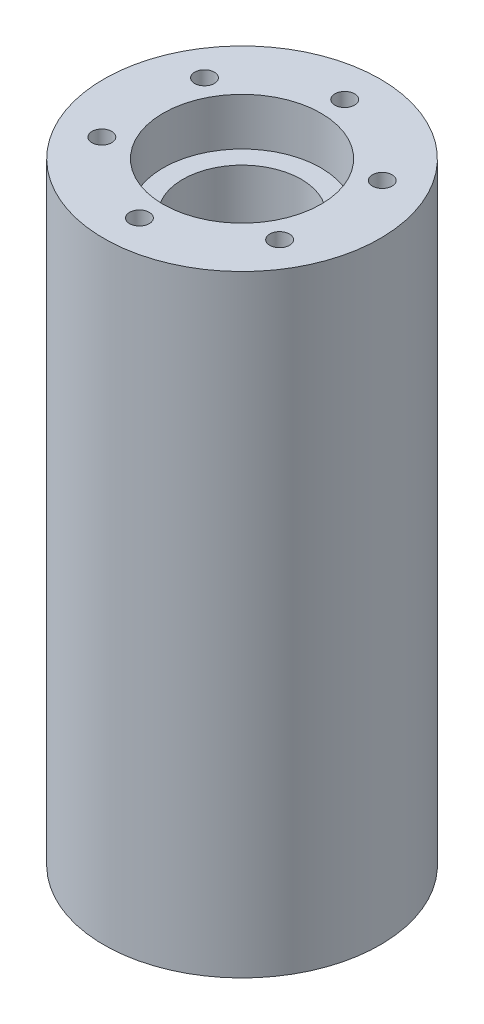
SolidWorks part; units mm, degrees
material "PA38 (3.3206)"
ref_plane "Płaszczyzna przednia" through (0, 0, 0) normal (0, 0, 1) x (1, 0, 0)
ref_plane "Płaszczyzna górna" through (0, 0, 0) normal (0, 1, 0) x (1, 0, 0)
ref_plane "Płaszczyzna prawa" through (0, 0, 0) normal (1, 0, 0) x (0, 0, -1)
sketch "Szkic1" plane through (0, 0, 0) normal (1, 0, 0) x (0, 0, -1)
  line L0 (0, -77.5) -> (0, 77.5) construction
  line L1 (-23.5, -77.5) -> (-35, -77.5)
  line L2 (-35, -77.5) -> (-35, 77.5)
  line L3 (-35, 77.5) -> (-20, 77.5)
  line L4 (-20, 77.5) -> (-20, 65.5)
  line L5 (-20, 65.5) -> (-15, 65.5)
  line L6 (-15, 65.5) -> (-15, -63.5)
  line L7 (-15, -63.5) -> (-23.5, -63.5)
  line L8 (-23.5, -63.5) -> (-23.5, -77.5)
  dimension "D1" = 30
  dimension "D2" = 47
  dimension "D3" = 14
  dimension "D4" = 70
  dimension "D5" = 40
  dimension "D6" = 12
  dimension "D7" = 155
revolve "Obrót1" add sketch "Szkic1" angle 360 about L0
hole_wizard "Otwór gwintowany M61" positions "Szkic2" profile "Szkic3" tap size "M6" standard "DIN"
sketch "Szkic2" plane through (0, -77.5, 0) normal (0, -1, 0) x (-1, 0, 0)
  line L1 (0, 0) -> (0, 30) construction
  point P0 (0, 30)
  dimension "D1" = 30
sketch "Szkic3" plane through (0, -77.5, -30) normal (1, 0, 0) x (0, 0, -1)
  line L0 (0, 0) -> (0, 18.5022)
  line L1 (0, 18.5022) -> (2.5, 17)
  line L2 (2.5, 17) -> (2.5, 0)
  line L5 (2.5, 0) -> (0, 0)
  line L10 (0, 18.5022) -> (-2.5, 17) construction
  line L11 (0, -6.35) -> (0, 107.95) construction
  dimension "Średnica wiertła gwintu" = 5
  dimension "Głębokość otworu gwintowanego" = 17
  dimension "Kąt wiertła" = 118
cosmetic thread "Gwint otworu1"
pattern_circular "Szyk kołowy1" count 6 over 360 about axis through (0, -77.5, 0) along (0, -1, 0) of "Otwór gwintowany M61" reverse direction yes
hole_wizard "Otwór gwintowany M62" positions "Szkic4" profile "Szkic5" tap size "M6" standard "DIN"
sketch "Szkic4" plane through (0, 77.5, 0) normal (0, 1, 0) x (1, 0, 0)
  line L0 (0, 0) -> (0, 26) construction
  point P0 (0, 26)
  dimension "D1" = 26
sketch "Szkic5" plane through (0, 77.5, -26) normal (1, 0, 0) x (0, 0, 1)
  line L0 (0, 0) -> (0, 18.5022)
  line L1 (0, 18.5022) -> (2.5, 17)
  line L2 (2.5, 17) -> (2.5, 0)
  line L5 (2.5, 0) -> (0, 0)
  line L10 (0, 18.5022) -> (-2.5, 17) construction
  line L11 (0, -6.35) -> (0, 107.95) construction
  dimension "Średnica wiertła gwintu" = 5
  dimension "Głębokość otworu gwintowanego" = 17
  dimension "Kąt wiertła" = 118
cosmetic thread "Gwint otworu2"
pattern_circular "Szyk kołowy2" count 6 over 360 about axis through (0, -77.5, 0) along (0, -1, 0) of "Otwór gwintowany M62"
